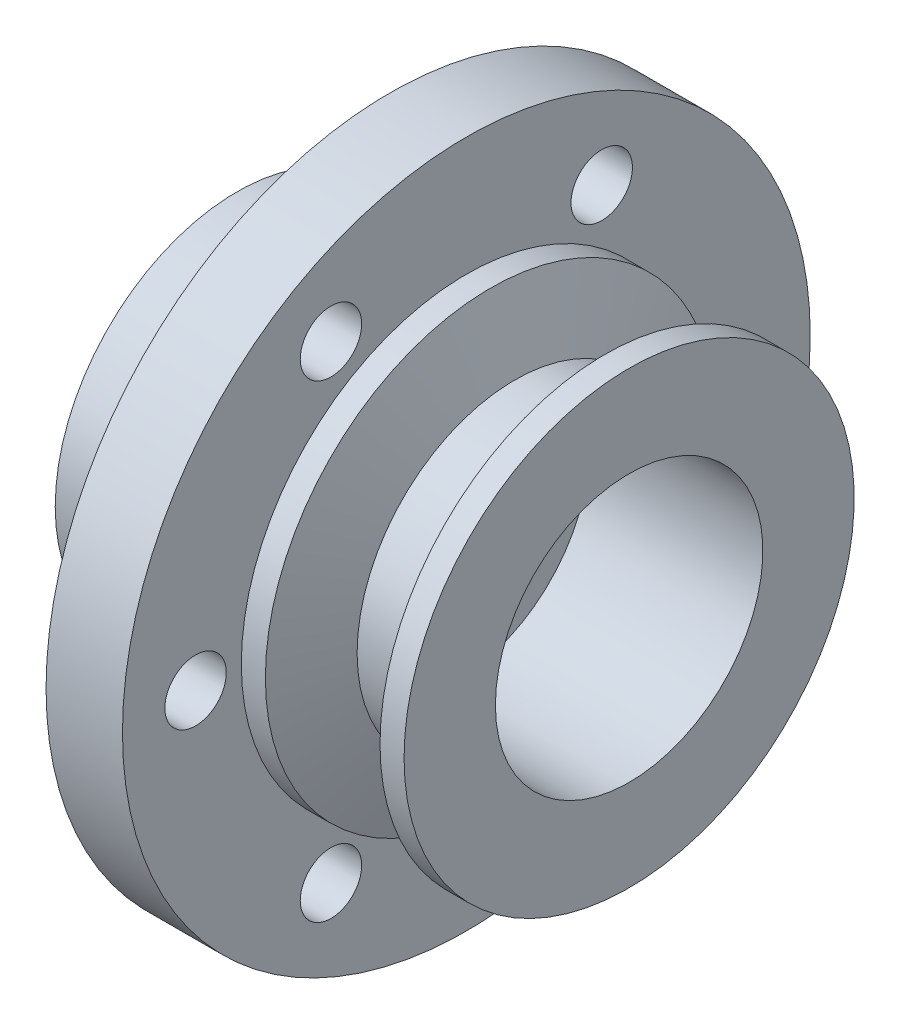
SolidWorks part; units mm, degrees
ref_plane "Front" through (0, 0, 0) normal (0, 0, 1) x (1, 0, 0)
ref_plane "Top" through (0, 0, 0) normal (0, 1, 0) x (1, 0, 0)
ref_plane "Right" through (0, 0, 0) normal (1, 0, 0) x (0, 0, -1)
sketch "Sketch1" plane through (0, 0, 0) normal (0, 0, 1) x (1, 0, 0)
  line L0 (-12.7, 15.1125) -> (0, 15.1125)
  line L1 (0, 15.1125) -> (0, 28.575)
  line L2 (0, 28.575) -> (6.35, 28.575)
  line L3 (6.35, 28.575) -> (6.35, 18.7005)
  line L4 (6.35, 18.7005) -> (8.35, 18.7005)
  line L5 (8.35, 18.7005) -> (10.3839, 13.1125)
  line L6 (10.3839, 13.1125) -> (15.8411, 13.1125)
  line L7 (15.8411, 13.1125) -> (17.875, 18.7005)
  line L8 (17.875, 18.7005) -> (19.875, 18.7005)
  line L9 (19.875, 18.7005) -> (19.875, 11.1125)
  line L10 (0, 0) -> (27.6559, 0) construction
  line L12 (19.875, 11.1125) -> (5.4125, 11.1125)
  line L13 (5.4125, 11.1125) -> (5.4125, 8.9375)
  line L14 (5.4125, 8.9375) -> (1.5875, 8.9375)
  line L15 (1.5875, 8.9375) -> (1.5875, 11.1125)
  line L16 (1.5875, 11.1125) -> (-12.7, 11.1125)
  line L17 (-12.7, 11.1125) -> (-12.7, 15.1125)
  line L18 (13.1125, 13.1125) -> (13.1125, 25.8182) construction
  dimension "D1" = 9.525
  dimension "D3" = 30.225
  dimension "D4" = 22.225
  dimension "D5" = 5.588
  dimension "D7" = 2
  dimension "D8" = 40
  dimension "D9" = 14.2875
  dimension "D10" = 14.4625
  dimension "D11" = 2
  dimension "D12" = 2
  dimension "D13" = 6.35
  dimension "D14" = 17.875
  dimension "D15" = 12.7
  dimension "D16" = 57.15
revolve "Revolve1" add sketch "Sketch1" angle 360 about L10
hole_wizard "1/4-20 Tapped Hole1" positions "Sketch2" profile "Sketch4" tap size "1/4-20" standard "ANSI Inch"
sketch "Sketch2" plane through (0, 0, 0) normal (-1, 0, 0) x (0, 0, 1)
  circle A0 centre (0, 0) radius 22.5 construction
  point P16 (-22.5, 0)
  point P24 (-11.25, 19.4856)
  point P25 (11.25, 19.4856)
  point P26 (22.5, 0)
  point P27 (11.25, -19.4856)
  point P28 (-11.25, -19.4856)
  dimension "D1" = 45
  dimension "D2" = 6
sketch "Sketch4" plane through (0, -19.4856, -11.25) normal (0, 1, 0) x (0, 0, 1)
  line L0 (0, 0) -> (0, 18.0438)
  line L1 (0, 18.0438) -> (2.5527, 16.51)
  line L2 (2.5527, 16.51) -> (2.5527, 0)
  line L5 (2.5527, 0) -> (0, 0)
  line L10 (0, 18.0438) -> (-2.5527, 16.51) construction
  line L11 (0, -6.35) -> (0, 107.95) construction
  dimension "Tap Drill Dia." = 5.1054
  dimension "Tap Drill Depth" = 16.51
  dimension "Drill Angle" = 118
cosmetic thread "Hole Thread1" parameters "D1"=12.7, "D2"=6.35
cosmetic thread "Hole Thread2" parameters "D1"=12.7, "D2"=6.35
cosmetic thread "Hole Thread3" parameters "D1"=12.7, "D2"=6.35
cosmetic thread "Hole Thread4" parameters "D1"=12.7, "D2"=6.35
cosmetic thread "Hole Thread7" parameters "D1"=12.7, "D2"=6.35
cosmetic thread "Hole Thread8" parameters "D1"=12.7, "D2"=6.35
